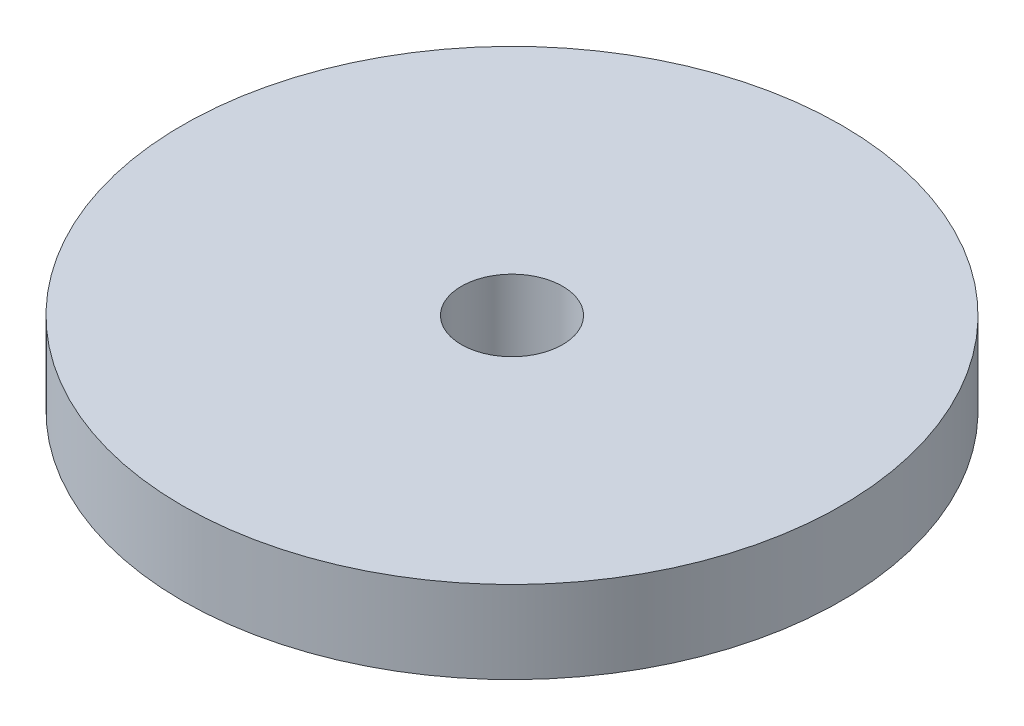
SolidWorks part; units mm, degrees
ref_plane "Front Plane" through (0, 0, 0) normal (0, 0, 1) x (1, 0, 0)
ref_plane "Top Plane" through (0, 0, 0) normal (0, 1, 0) x (1, 0, 0)
ref_plane "Right Plane" through (0, 0, 0) normal (1, 0, 0) x (0, 0, -1)
sketch "Sketch1" plane through (0, 0, 0) normal (0, 1, 0) x (1, 0, 0)
  circle A0 centre (0, 0) radius 14
  dimension "D1" = 28
extrude "Boss-Extrude1" add sketch "Sketch1" along normal blind 4
sketch "Sketch2" plane through (0, 0, 0) normal (0, -1, 0) x (1, 0, 0)
  circle A0 centre (0, 0) radius 6.5
  circle A1 centre (0, 0) radius 14
  dimension "D1" = 13
extrude "Cut-Extrude1" cut sketch "Sketch2" against normal blind 0.5
sketch "Sketch3" plane through (0, 4, 0) normal (0, 1, 0) x (1, 0, 0)
  circle A0 centre (0, 0) radius 2.15
  dimension "D1" = 4.3
extrude "Cut-Extrude2" cut sketch "Sketch3" against normal up to surface (4 mm away) up to face at (0, 0, -6.5)
